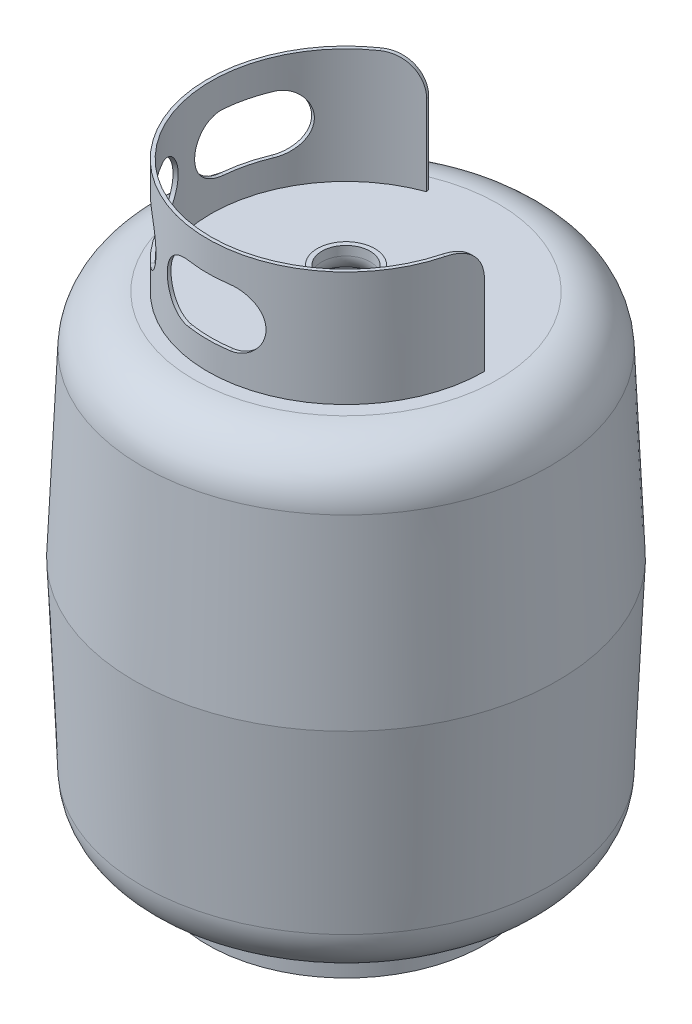
SolidWorks part; units mm, degrees
material "1060 Alloy"
ref_plane "Front Plane" through (0, 0, 0) normal (0, 0, 1) x (1, 0, 0)
ref_plane "Top Plane" through (0, 0, 0) normal (0, 1, 0) x (1, 0, 0)
ref_plane "Right Plane" through (0, 0, 0) normal (1, 0, 0) x (0, 0, -1)
sketch "Sketch1" plane through (0, 0, 0) normal (0, 0, 1) x (1, 0, 0)
  line L0 (0, 402.5) -> (0, 0) construction
  line L1 (-132.5428, 0) -> (132.5428, 0)
  line L2 (177.5, 43.0371) -> (184.4077, 201.25)
  line L3 (-177.5, 43.0371) -> (-184.4077, 201.25)
  line L4 (184.4077, 201.25) -> (177.5, 359.4629)
  line L5 (-184.4077, 201.25) -> (-177.5, 359.4629)
  line L6 (132.5428, 402.5) -> (37, 402.5)
  line L7 (-132.5428, 402.5) -> (-37, 402.5)
  line L8 (25, 414.5) -> (25, 422.5)
  line L9 (-25, 414.5) -> (-25, 422.5)
  line L10 (-21, 414.5) -> (-21, 422.5)
  line L11 (-132.5428, 398.5) -> (-37, 398.5)
  line L12 (-180.4039, 201.25) -> (-173.5038, 359.2884)
  line L13 (-173.5038, 43.2116) -> (-180.4039, 201.25)
  line L14 (-132.5428, 4) -> (132.5428, 4)
  line L15 (173.5038, 43.2116) -> (180.4039, 201.25)
  line L16 (180.4039, 201.25) -> (173.5038, 359.2884)
  line L17 (132.5428, 398.5) -> (37, 398.5)
  line L18 (21, 414.5) -> (21, 422.5)
  line L19 (-25, 422.5) -> (-21, 422.5)
  line L20 (21, 422.5) -> (25, 422.5)
  arc A0 (132.5428, 0) -> (177.5, 43.0371) centre (132.5428, 45) ccw
  arc A1 (-132.5428, 0) -> (-177.5, 43.0371) centre (-132.5428, 45) cw
  arc A2 (177.5, 359.4629) -> (132.5428, 402.5) centre (132.5428, 357.5) ccw
  arc A3 (-177.5, 359.4629) -> (-132.5428, 402.5) centre (-132.5428, 357.5) cw
  arc A4 (37, 402.5) -> (25, 414.5) centre (37, 414.5) cw
  arc A5 (-37, 402.5) -> (-25, 414.5) centre (-37, 414.5) ccw
  arc A6 (-37, 398.5) -> (-21, 414.5) centre (-37, 414.5) ccw
  arc A7 (-173.5038, 359.2884) -> (-132.5428, 398.5) centre (-132.5428, 357.5) cw
  arc A8 (-132.5428, 4) -> (-173.5038, 43.2116) centre (-132.5428, 45) cw
  arc A9 (132.5428, 4) -> (173.5038, 43.2116) centre (132.5428, 45) ccw
  arc A10 (173.5038, 359.2884) -> (132.5428, 398.5) centre (132.5428, 357.5) ccw
  arc A11 (37, 398.5) -> (21, 414.5) centre (37, 414.5) cw
  point P6 (0, 0)
  point P26 (-25, 418.5)
  point P35 (0, 201.25)
  dimension "D4" = 12
  dimension "D5" = 45
  dimension "D8" = 45
  dimension "D1" = 402.5
  dimension "D2" = 355
  dimension "D3" = 50
  dimension "D6" = 92.5
  dimension "D7" = 92.5
  dimension "D9" = 20
  dimension "D10" = 4
revolve "Revolve2" add sketch "Sketch1" angle 360 about L0 region at (-4.6099, 2, 0)
sketch "Sketch2" plane through (0, 0, 0) normal (0, -1, 0) x (1, 0, 0)
  circle A0 centre (0, 0) radius 120.5428
  circle A1 centre (0, 0) radius 117.5428
  circle A2 centre (0, 0) radius 132.5428 construction
  dimension "D2" = 12
  dimension "D1" = 3
extrude "Boss-Extrude1" add sketch "Sketch2" along normal blind 30
sketch "Sketch3" plane through (0, 402.5, 0) normal (0, 1, 0) x (1, 0, 0)
  line L0 (-40.202, 110.4541) -> (-41.2281, 113.2732)
  line L1 (117.5428, 0) -> (120.5428, 0)
  arc A0 (-40.202, 110.4541) -> (117.5428, 0) centre (0, 0) ccw
  arc A1 (-41.2281, 113.2732) -> (120.5428, 0) centre (0, 0) ccw
  circle A2 centre (0, 0) radius 132.5428 construction
  circle A3 centre (0, 0) radius 120.5428 construction
  circle A4 centre (0, 0) radius 117.5428 construction
  point P1 (0, 0)
  point P12 (0, 0)
  point P13 (0, 0)
  point P14 (0, 0)
  point P15 (0, 0)
  point P16 (-32.7303, 113.1872)
  dimension "D2" = 12
  dimension "D3" = 110
  dimension "D1" = 3
extrude "Boss-Extrude2" add sketch "Sketch3" along normal blind 100
fillet "Fillet1" radius 30 2 edges at (-40.715, 502.5, -111.8637) (119.0428, 502.5, 0)
sketch "Sketch4" plane through (0, 0, 0) normal (0, 0, 1) x (1, 0, 0)
  line L0 (-18, 451.5691) -> (18, 451.5691) construction
  line L1 (-18, 476.5691) -> (18, 476.5691)
  line L2 (-18, 426.5691) -> (18, 426.5691)
  arc A0 (-18, 476.5691) -> (-18, 426.5691) centre (-18, 451.5691) ccw
  arc A1 (18, 426.5691) -> (18, 476.5691) centre (18, 451.5691) ccw
  point P2 (0, 451.5691)
  point P7 (-43, 451.5691)
  point P8 (43, 451.5691)
  point P9 (0, 0)
  dimension "D1" = 86
  dimension "D2" = 50
extrude "Cut-Extrude1" cut sketch "Sketch4" along normal through all
pattern_circular "CirPattern1" count 3 every 52 about axis through (0, 502.5, 0) along (0, -1, 0) of "Cut-Extrude1"
equation "\"A\"= 355"
equation "\"B\"= 402.5"
equation "\"D1@Sketch1\"=\"B\""
equation "\"D2@Sketch1\"=\"A\""
